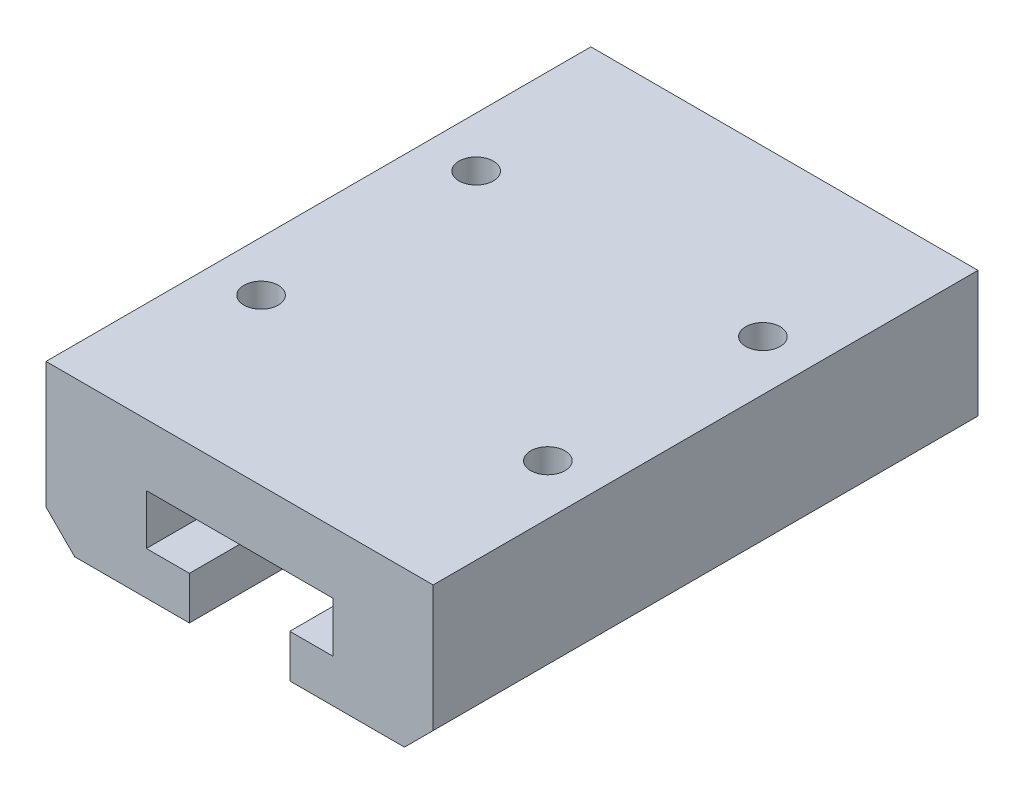
SolidWorks part; units mm, degrees
ref_plane "Ebene vorne" through (0, 0, 0) normal (0, 0, 1) x (1, 0, 0)
ref_plane "Ebene oben" through (0, 0, 0) normal (0, 1, 0) x (1, 0, 0)
ref_plane "Ebene rechts" through (0, 0, 0) normal (1, 0, 0) x (0, 0, -1)
sketch "Skizze1" plane through (0, 0, 0) normal (0, 0, 1) x (1, 0, 0)
  line L0 (-3.5, 0) -> (-3.5, 3)
  line L1 (-3.5, 3) -> (-6.5, 3)
  line L2 (-6.5, 3) -> (-6.5, 6.5)
  line L3 (-6.5, 6.5) -> (6.5, 6.5)
  line L4 (0, 6.5) -> (0, 10.8) construction
  line L5 (13.5, 10.8) -> (-13.5, 10.8)
  line L6 (-13.5, 10.8) -> (-13.5, 0)
  line L7 (-13.5, 0) -> (-3.5, 0)
  line L8 (13.5, 0) -> (3.5, 0)
  line L9 (13.5, 10.8) -> (13.5, 0)
  line L10 (6.5, 3) -> (6.5, 6.5)
  line L11 (3.5, 3) -> (6.5, 3)
  line L12 (3.5, 0) -> (3.5, 3)
  dimension "D1" = 27
  dimension "D2" = 10.8
  dimension "D3" = 10
  dimension "D4" = 3.5
  dimension "D5" = 3
  dimension "D6" = 13
extrude "Aufsatz-Linear austragen1" add sketch "Skizze1" along normal blind 19 and the other way blind 19
hole_wizard "Stirnsenkung für M2 Flachkopfschraube mit Schlitz1" positions "Skizze2" profile "Skizze3" counterbore size "M2" standard "DIN" end condition through all
sketch "Skizze2" plane through (0, 0, 0) normal (0, -1, 0) x (-1, 0, 0)
  line L0 (0, 0) -> (0, -19.1054) construction
  line L2 (0, 0) -> (-13.5, 0) construction
  line L3 (-13.5, 19) -> (-13.5, -19) construction
  point P0 (-10, -7.5)
  point P2 (-10, 7.5)
  point P4 (10, -7.5)
  point P6 (10, 7.5)
  dimension "D1" = 15
  dimension "D2" = 20
sketch "Skizze3" plane through (10, 0, 7.5) normal (1, 0, 0) x (0, 0, -1)
  line L0 (0, 0) -> (0, 10.8)
  line L1 (0, 10.8) -> (1.2, 10.8)
  line L3 (1.2, 10.8) -> (1.2, 1.6)
  line L4 (1.2, 1.6) -> (2.5, 1.6)
  line L5 (2.5, 1.6) -> (2.5, 0)
  line L7 (2.5, 0) -> (0, 0)
  line L11 (0, -6.35) -> (0, 107.95) construction
  dimension "Bohrerdurchmesser" = 2.4
  dimension "Bohrungstiefe" = 10.8
  dimension "Senkdurchmesser2" = 5
  dimension "Senktiefe2" = 1.6
chamfer "Fase1" distance 2 angle 45 2 edges at (-13.5, 0, 0) (13.5, 0, 0)
